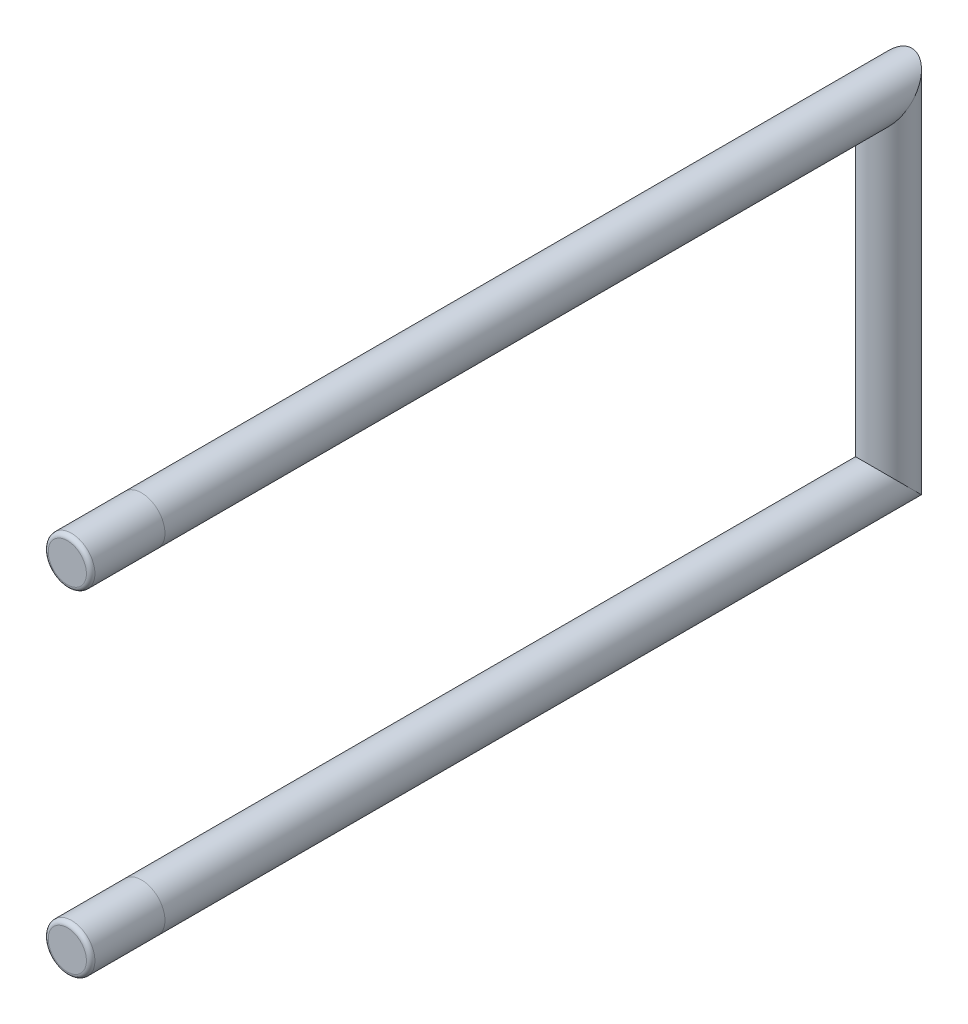
SolidWorks part; units mm, degrees
ref_plane "前视基准面" through (0, 0, 0) normal (0, 0, 1) x (1, 0, 0)
ref_plane "上视基准面" through (0, 0, 0) normal (0, 1, 0) x (1, 0, 0)
ref_plane "右视基准面" through (0, 0, 0) normal (1, 0, 0) x (0, 0, -1)
sketch "草图1" plane through (0, 0, 0) normal (0, 0, 1) x (1, 0, 0)
  circle A0 centre (0, 0) radius 11
  dimension "D1" = 22
extrude "拉伸1" add sketch "草图1" along normal blind 352
sketch "草图2" plane through (0, 0, 0) normal (0, 1, 0) x (1, 0, 0)
  circle A0 centre (0, 0) radius 11
  dimension "D1" = 22
extrude "拉伸2" add sketch "草图2" along normal blind 158
ref_axis "基准轴1" through (0, 178.0544, 0) along (0, -1, 0)
pattern_linear "阵列(线性)1" count 2 spacing 158 along (0, 1, 0) of "拉伸1"
sketch "草图3" plane through (0, 0, 352) normal (0, 0, 1) x (1, 0, 0)
  circle A0 centre (0, 158) radius 10.9995
  circle A1 centre (0, 0) radius 10.9995
  circle A2 centre (0, 158) radius 11 construction
  dimension "D1" = 21.999
extrude "拉伸3" add sketch "草图3" along normal blind 35
chamfer "倒角1" distance 21.999 angle 45 2 edges at (0, 0, 0) (0, 158, 0)
fillet "圆角1" radius 2 2 edges at (10.9995, 0, 387) (10.9995, 158, 387)
